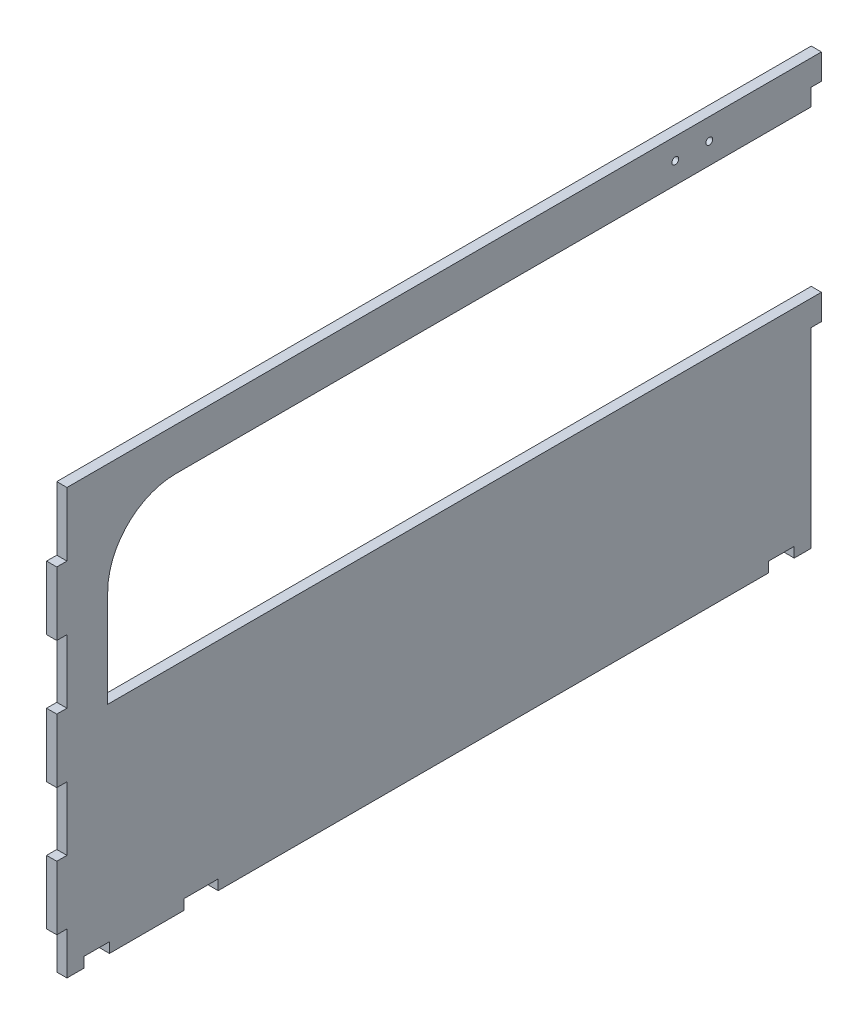
SolidWorks part; units mm, degrees
ref_plane "Front" through (0, 0, 0) normal (0, 0, 1) x (1, 0, 0)
ref_plane "Top" through (0, 0, 0) normal (0, 1, 0) x (1, 0, 0)
ref_plane "Right" through (0, 0, 0) normal (1, 0, 0) x (0, 0, -1)
sketch "Sketch1" plane through (0, 0, 0) normal (1, 0, 0) x (0, 0, -1)
  line L0 (450, 225) -> (450, 250)
  line L1 (0, 0) -> (450, 0)
  line L2 (0, 0) -> (0, 250)
  line L3 (0, 250) -> (450, 250)
  line L4 (450, 0) -> (450, 127.5)
  line L5 (450, 225) -> (30, 225)
  line L7 (450, 127.5) -> (30, 127.5)
  line L8 (30, 225) -> (30, 127.5)
  dimension "D1" = 420
  dimension "D2" = 250
  dimension "D3" = 127.5
  dimension "D4" = 25
  dimension "D5" = 30
extrude "Boss-Extrude1" add sketch "Sketch1" along normal blind 6
sketch "Sketch2" plane through (6, 0, 0) normal (1, 0, 0) x (0, 0, -1)
  line L1 (0, 250) -> (6, 250)
  line L2 (0, 250) -> (0, 212.5)
  line L3 (0, 212.5) -> (6, 212.5)
  line L4 (6, 250) -> (6, 212.5)
  dimension "D1" = 6
  dimension "D2" = 37.5
extrude "Cut-Extrude1" cut sketch "Sketch2" against normal blind 6
pattern_linear "LPattern1" count 4 spacing 75 along (0, -1, 0) of "Cut-Extrude1"
fillet "Fillet1" radius 40 1 edges at (3, 225, -30)
sketch "Sketch3" plane through (0, 0, 0) normal (-1, 0, 0) x (0, 0, 1)
  line L0 (-450, 0) -> (-450, 127.5) construction
  line L1 (-450, 235) -> (-444, 235)
  line L2 (-450, 235) -> (-450, 225)
  line L3 (-450, 225) -> (-444, 225)
  line L4 (-444, 235) -> (-444, 225)
  line L5 (-70, 225) -> (-450, 225) construction
  line L7 (-450, 112.5) -> (-444, 112.5)
  line L8 (-450, 112.5) -> (-450, 0)
  line L9 (-450, 0) -> (-444, 0)
  line L10 (-444, 112.5) -> (-444, 0)
  line L12 (-450, 225) -> (-450, 250) construction
  line L13 (-450, 127.5) -> (-30, 127.5) construction
  line L14 (-6, 0) -> (-450, 0) construction
  dimension "D1" = 6
  dimension "D2" = 10
  dimension "D4" = 15
extrude "Cut-Extrude2" cut sketch "Sketch3" against normal through all
sketch "Sketch4" plane through (0, 0, 0) normal (-1, 0, 0) x (0, 0, 1)
  line L0 (-6, 0) -> (-444, 0) construction
  line L1 (-16, 0) -> (-31, 0)
  line L2 (-16, 0) -> (-16, 6)
  line L3 (-16, 6) -> (-31, 6)
  line L4 (-31, 0) -> (-31, 6)
  line L5 (-6, 62.5) -> (-6, 100) construction
  line L6 (-6, 0) -> (-444, 0) construction
  line L7 (-434, 0) -> (-419, 0)
  line L8 (-434, 0) -> (-434, 6)
  line L9 (-434, 6) -> (-419, 6)
  line L10 (-419, 0) -> (-419, 6)
  line L11 (-444, 0) -> (-444, 112.5) construction
  dimension "D1" = 10
  dimension "D2" = 15
  dimension "D3" = 6
  dimension "D4" = 10
extrude "Cut-Extrude3" cut sketch "Sketch4" against normal through all
sketch "Sketch5" plane through (0, 0, 0) normal (-1, 0, 0) x (0, 0, 1)
  line L0 (-450, 235) -> (-450, 250) construction
  line L1 (-450, 250) -> (-6, 250) construction
  circle A0 centre (-384, 237.5) radius 2
  circle A1 centre (-364, 237.5) radius 2
  dimension "D3" = 4
  dimension "D1" = 66
  dimension "D2" = 12.5
  dimension "D4" = 20
extrude "Cut-Extrude4" cut sketch "Sketch5" against normal through all
sketch "Sketch6" plane through (0, 0, 0) normal (-1, 0, 0) x (0, 0, 1)
  line L0 (-31, 0) -> (-419, 0) construction
  line L1 (-75, 0) -> (-95, 0)
  line L2 (-75, 0) -> (-75, 6)
  line L3 (-75, 6) -> (-95, 6)
  line L4 (-95, 0) -> (-95, 6)
  line L6 (-16, 6) -> (-31, 6) construction
  line L7 (0, 62.5) -> (0, 25) construction
  point P8 (-57.192, 6.0441)
  dimension "D1" = 20
  dimension "D2" = 75
extrude "Cut-Extrude5" cut sketch "Sketch6" against normal through all
